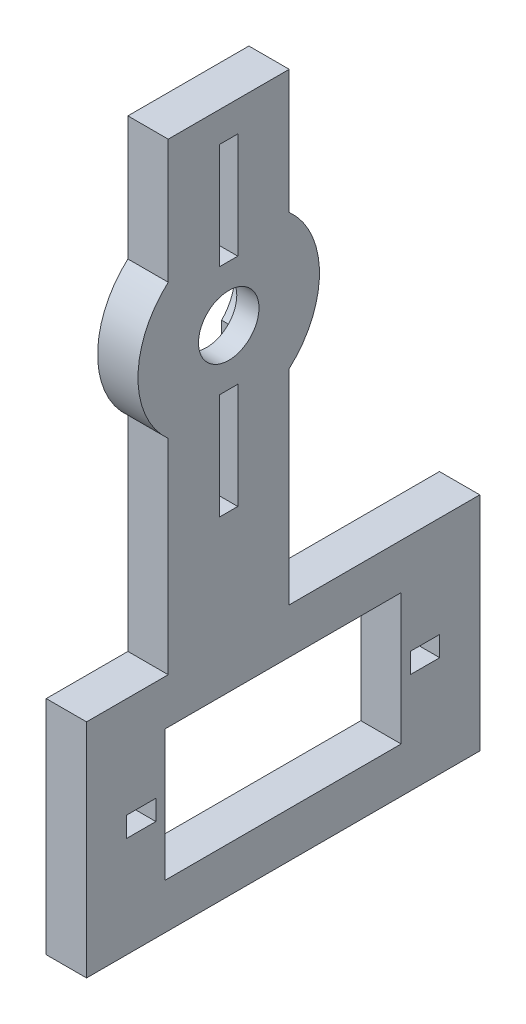
SolidWorks part; units mm, degrees
ref_plane "Front Plane" through (0, 0, 0) normal (0, 0, 1) x (1, 0, 0)
ref_plane "Top Plane" through (0, 0, 0) normal (0, 1, 0) x (1, 0, 0)
ref_plane "Right Plane" through (0, 0, 0) normal (1, 0, 0) x (0, 0, -1)
sketch "Sketch1" plane through (0, 0, 0) normal (1, 0, 0) x (0, 0, -1)
  circle A0 centre (52, 18) radius 9
extrude "Boss-Extrude1" add sketch "Sketch1" along normal blind 4 from offset 55.6
sketch "Sketch2" plane through (0, 0, 0) normal (0, 0, 1) x (1, 0, 0)
  line L1 (55.6, -12) -> (59.6, -12)
  line L2 (55.6, -12) -> (55.6, 37)
  line L3 (55.6, 37) -> (59.6, 37)
  line L4 (59.6, -12) -> (59.6, 37)
extrude "Boss-Extrude2" add sketch "Sketch2" along normal blind 12 from offset 58 offset against normal yes
sketch "Sketch3" plane through (0, 0, 0) normal (0, 0, 1) x (1, 0, 0)
  line L1 (55.6, -31) -> (59.6, -31)
  line L2 (55.6, -31) -> (55.6, -9)
  line L3 (55.6, -9) -> (59.6, -9)
  line L4 (59.6, -31) -> (59.6, -9)
extrude "Boss-Extrude3" add sketch "Sketch3" along normal blind 39 from offset 76.9 offset against normal yes
sketch "Sketch4" plane through (0, 0, 0) normal (1, 0, 0) x (0, 0, -1)
  circle A0 centre (52, 18) radius 4.6
extrude "Boss-Extrude4" add sketch "Sketch4" along normal blind 2.3 from offset 55.1 separate body
combine bodies "Combine1" operation type subtract main body 103 bodies to subtract 104
sketch "Sketch5" plane through (0, 0, 0) normal (0, 0, 1) x (1, 0, 0)
  line L1 (55.1, 18) -> (57.4, 18)
  line L2 (55.1, 18) -> (55.1, 35.5)
  line L3 (55.1, 35.5) -> (57.4, 35.5)
  line L4 (57.4, 18) -> (57.4, 35.5)
extrude "Boss-Extrude5" add sketch "Sketch5" along normal blind 6.6 from offset 55.3 separate body offset against normal yes
combine bodies "Combine2" operation type subtract main body 105 bodies to subtract 106
sketch "Sketch6" plane through (0, 0, 0) normal (0, 0, 1) x (1, 0, 0)
  line L1 (54.6, 23.5) -> (60.6, 23.5)
  line L2 (54.6, 23.5) -> (54.6, 34)
  line L3 (54.6, 34) -> (60.6, 34)
  line L4 (60.6, 23.5) -> (60.6, 34)
extrude "Boss-Extrude6" add sketch "Sketch6" along normal blind 1.8 from offset 52.9 separate body offset against normal yes
combine bodies "Combine3" operation type subtract main body 107 bodies to subtract 108
sketch "Sketch7" plane through (0, 0, 0) normal (0, 0, 1) x (1, 0, 0)
  line L1 (55.1, 0.5) -> (57.4, 0.5)
  line L2 (55.1, 0.5) -> (55.1, 18)
  line L3 (55.1, 18) -> (57.4, 18)
  line L4 (57.4, 0.5) -> (57.4, 18)
extrude "Boss-Extrude7" add sketch "Sketch7" along normal blind 6.6 from offset 55.3 separate body offset against normal yes
combine bodies "Combine4" operation type subtract main body 109 bodies to subtract 110
sketch "Sketch8" plane through (0, 0, 0) normal (0, 0, 1) x (1, 0, 0)
  line L1 (54.6, 2) -> (60.6, 2)
  line L2 (54.6, 2) -> (54.6, 12.5)
  line L3 (54.6, 12.5) -> (60.6, 12.5)
  line L4 (60.6, 2) -> (60.6, 12.5)
extrude "Boss-Extrude8" add sketch "Sketch8" along normal blind 1.8 from offset 52.9 separate body offset against normal yes
combine bodies "Combine5" operation type subtract main body 111 bodies to subtract 112
sketch "Sketch9" plane through (0, 0, 0) normal (1, 0, 0) x (0, 0, -1)
  circle A0 centre (52, 18) radius 3
extrude "Boss-Extrude9" add sketch "Sketch9" along normal blind 6 from offset 54.6 separate body
combine bodies "Combine6" operation type subtract main body 113 bodies to subtract 114
sketch "Sketch10" plane through (0, 0, 0) normal (0, 0, 1) x (1, 0, 0)
  line L1 (54.6, -26.5) -> (60.6, -26.5)
  line L2 (54.6, -26.5) -> (54.6, -13.5)
  line L3 (54.6, -13.5) -> (60.6, -13.5)
  line L4 (60.6, -26.5) -> (60.6, -13.5)
extrude "Boss-Extrude10" add sketch "Sketch10" along normal blind 23.4 from offset 69.1 separate body offset against normal yes
combine bodies "Combine7" operation type subtract main body 115 bodies to subtract 116
sketch "Sketch11" plane through (0, 0, 0) normal (0, 0, 1) x (1, 0, 0)
  line L1 (54.6, -21) -> (60.6, -21)
  line L2 (54.6, -21) -> (54.6, -19)
  line L3 (54.6, -19) -> (60.6, -19)
  line L4 (60.6, -21) -> (60.6, -19)
extrude "Boss-Extrude11" add sketch "Sketch11" along normal blind 2.9 from offset 72.925 separate body offset against normal yes
combine bodies "Combine8" operation type subtract main body 117 bodies to subtract 118
sketch "Sketch12" plane through (0, 0, 0) normal (0, 0, 1) x (1, 0, 0)
  line L1 (54.6, -21) -> (60.6, -21)
  line L2 (54.6, -21) -> (54.6, -19)
  line L3 (54.6, -19) -> (60.6, -19)
  line L4 (60.6, -21) -> (60.6, -19)
extrude "Boss-Extrude12" add sketch "Sketch12" along normal blind 2.9 from offset 44.775 separate body offset against normal yes
combine bodies "Combine9" operation type subtract main body 119 bodies to subtract 120
